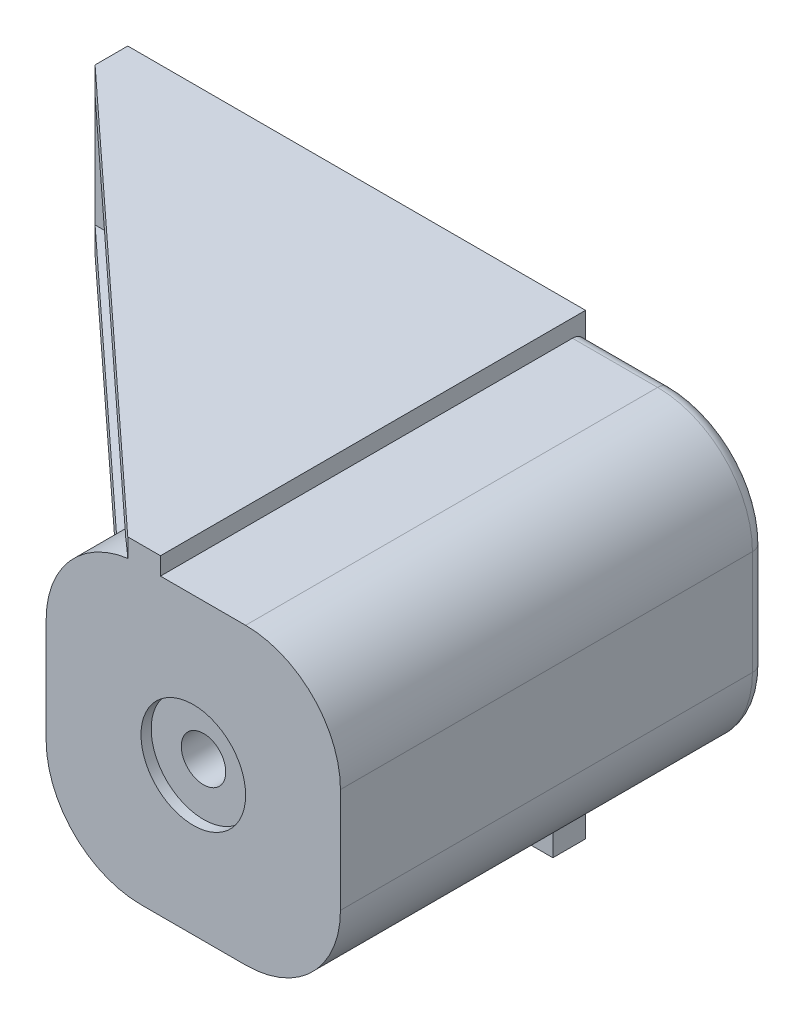
SolidWorks part; units mm, degrees
ref_plane "Front Plane" through (0, 0, 0) normal (0, 0, 1) x (1, 0, 0)
ref_plane "Top Plane" through (0, 0, 0) normal (0, 1, 0) x (1, 0, 0)
ref_plane "Right Plane" through (0, 0, 0) normal (1, 0, 0) x (0, 0, -1)
sketch "Sketch1" plane through (0, 0, 0) normal (0, 0, 1) x (1, 0, 0)
  line L1 (-8, 18) -> (8, 18)
  line L2 (-18, 8) -> (-18, -8)
  line L3 (-8, -18) -> (8, -18)
  line L4 (18, 8) -> (18, -8)
  line L5 (-18, 18) -> (18, -18) construction
  line L6 (-18, -18) -> (18, 18) construction
  line L7 (-8, 22.5) -> (8, 22.5)
  line L8 (-22.5, 8) -> (-22.5, -8)
  line L9 (-8, -22.5) -> (8, -22.5)
  line L10 (22.5, 8) -> (22.5, -8)
  line L11 (-22.5, 22.5) -> (22.5, -22.5) construction
  line L12 (-22.5, -22.5) -> (22.5, 22.5) construction
  arc A0 (8, -18) -> (18, -8) centre (8, -8) ccw
  arc A1 (-18, -8) -> (-8, -18) centre (-8, -8) ccw
  arc A2 (-8, 18) -> (-18, 8) centre (-8, 8) ccw
  arc A3 (8, 18) -> (18, 8) centre (8, 8) cw
  arc A4 (8, 22.5) -> (22.5, 8) centre (8, 8) cw
  arc A5 (8, -22.5) -> (22.5, -8) centre (8, -8) ccw
  arc A6 (-22.5, -8) -> (-8, -22.5) centre (-8, -8) ccw
  arc A7 (-8, 22.5) -> (-22.5, 8) centre (-8, 8) ccw
  point P0 (0, 0)
  point P18 (0, 0)
  dimension "D3" = 10
  dimension "D6" = 14.5
  dimension "D1" = 36
  dimension "D2" = 36
  dimension "D4" = 45
  dimension "D5" = 45
extrude "Boss-Extrude1" add sketch "Sketch1" along normal blind 65 contours A3 L1 A2 L2 A1 L3 A0 L4 | L7 A4 L10 A5 L9 A6 L8 A7 region at (0, 0, 0)
fillet "Fillet1" radius 2 16 edges at (-22.5, 0, 0) (-18.253, -18.253, 0) (0, -22.5, 0) (18.253, -18.253, 0) (22.5, 0, 0) (18.253, 18.253, 0) (0, 22.5, 0) (-18.253, 18.253, 0) (15.0711, -15.0711, 0) (0, -18, 0) (-15.0711, -15.0711, 0) (-18, 0, 0) (-15.0711, 15.0711, 0) (0, 18, 0) (15.0711, 15.0711, 0) (18, 0, 0)
sketch "Sketch2" plane through (0, 0, 65) normal (0, 0, 1) x (1, 0, 0)
  line L1 (8, -22.5) -> (-8, -22.5)
  line L2 (22.5, -8) -> (22.5, 8)
  line L3 (8, 22.5) -> (-8, 22.5)
  line L4 (-22.5, -8) -> (-22.5, 8)
  line L5 (22.5, -22.5) -> (-22.5, 22.5) construction
  line L6 (22.5, 22.5) -> (-22.5, -22.5) construction
  arc A0 (-8, -22.5) -> (-22.5, -8) centre (-8, -8) cw
  arc A1 (8, -22.5) -> (22.5, -8) centre (8, -8) ccw
  arc A2 (22.5, 8) -> (8, 22.5) centre (8, 8) ccw
  arc A3 (-8, 22.5) -> (-22.5, 8) centre (-8, 8) ccw
  point P0 (0, 0)
  dimension "D3" = 14.5
  dimension "D1" = 45
  dimension "D2" = 45
extrude "Boss-Extrude2" add sketch "Sketch2" against normal blind 10
sketch "Sketch3" plane through (0, 0, 65) normal (0, 0, 1) x (1, 0, 0)
  circle A0 centre (0, 0) radius 3.4
  dimension "D1" = 6.8
extrude "Cut-Extrude1" cut sketch "Sketch3" against normal through all contours A0
fillet "Fillet2" [suppressed] radius 3
sketch "Sketch4" plane through (0, 0, 65) normal (0, 0, 1) x (1, 0, 0)
  circle A0 centre (0, 0) radius 8
  dimension "D1" = 16
extrude "Cut-Extrude2" cut sketch "Sketch4" against normal blind 1.56
sketch "Sketch5" plane through (0, 0, 0) normal (0, 0, 1) x (1, 0, 0)
  line L0 (22.5, -8) -> (22.5, 8) construction
  line L1 (-75.02, 25.2) -> (-5.02, 25.2)
  line L2 (-75.02, 25.2) -> (-75.02, -0.2)
  line L3 (-30.42, -44.8) -> (-5.02, -44.8)
  line L4 (-5.02, 25.2) -> (-5.02, 20)
  line L5 (8, 22.5) -> (-8, 22.5) construction
  line L6 (-75.02, -0.2) -> (-30.42, -44.8)
  line L7 (-5.02, 20) -> (-8, 20)
  line L8 (8, 20) -> (-8, 20) construction
  line L9 (-20, 8) -> (-20, -8)
  line L10 (-8, -20) -> (-5.02, -20)
  line L11 (-8, -20) -> (8, -20) construction
  line L12 (-5.02, -20) -> (-5.02, -44.8)
  arc A1 (-8, -20) -> (-20, -8) centre (-8, -8) cw
  arc A2 (-8, 20) -> (-20, 8) centre (-8, 8) ccw
  dimension "D1" = 27.52
  dimension "D2" = 2.7
  dimension "D3" = 70
  dimension "D4" = 70
  dimension "D5" = 25.4
  dimension "D6" = 25.4
extrude "Boss-Extrude3" add sketch "Sketch5" along normal blind 5 contours L1 L4 L7 A2 L9 A1 L10 L12 L3 L6 L2
sketch "Sketch6" plane through (0, 25.2, 0) normal (0, 1, 0) x (1, 0, 0)
  line L0 (-75.02, 0) -> (-75.02, -5)
  line L1 (-5.02, 0) -> (-5.02, -65)
  line L2 (-5.02, -65) -> (-10.02, -65)
  line L3 (-10.02, -65) -> (-75.02, -5)
  line L4 (-5.02, 0) -> (-75.02, 0)
  dimension "D1" = 65
  dimension "D2" = 5
extrude "Boss-Extrude4" add sketch "Sketch6" against normal blind 4 contours L3 L0 L4 L1 L2
ref_plane "Plane1" through (0, 0, 0) normal (0, 1, 0) x (1, 0, 0)
sketch "Sketch7" plane through (0, 0, 0) normal (0, 1, 0) x (1, 0, 0)
  line L0 (-75.02, -5) -> (-22.5, -53.48)
  line L1 (-10.02, -65) -> (-75.02, -5) construction
  line L2 (-22.5, -65) -> (-22.5, -5) construction
  line L3 (-22.5, -53.48) -> (-22.5, -5)
  line L4 (-22.5, -5) -> (-75.02, -5)
  line L5 (-22.5, -65) -> (-22.5, -5) construction
extrude "Boss-Extrude5" add sketch "Sketch7" along normal blind 4
